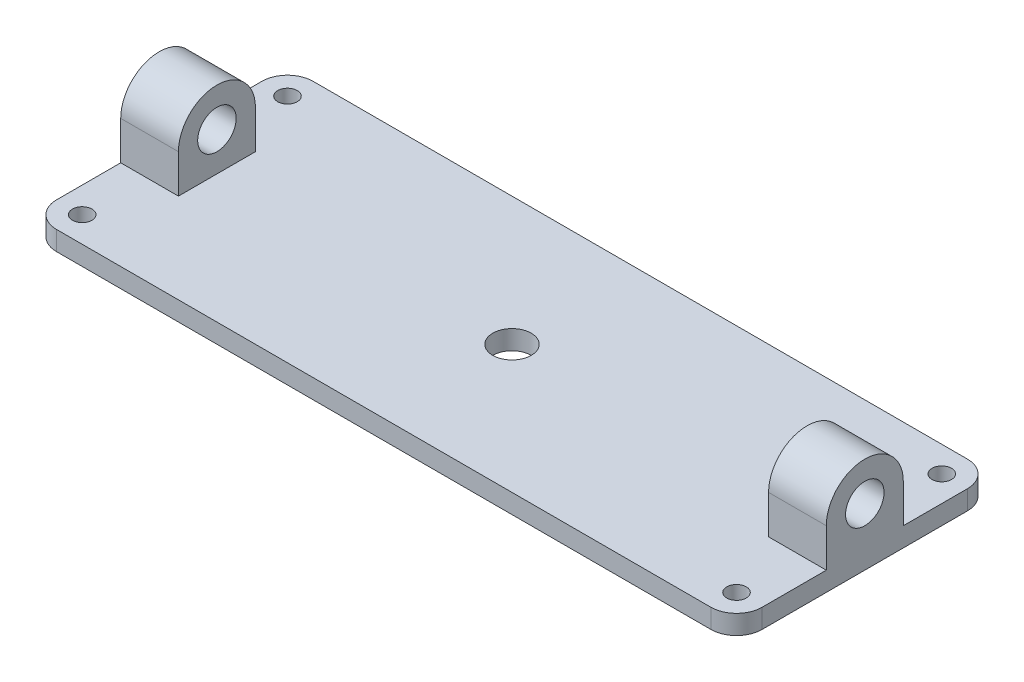
SolidWorks part; units mm, degrees
ref_plane "Front Plane" through (0, 0, 0) normal (0, 0, 1) x (1, 0, 0)
ref_plane "Top Plane" through (0, 0, 0) normal (0, 1, 0) x (1, 0, 0)
ref_plane "Right Plane" through (0, 0, 0) normal (1, 0, 0) x (0, 0, -1)
sketch "Sketch1" plane through (0, 0, 0) normal (0, 1, 0) x (1, 0, 0)
  line L0 (-349.25, 0) -> (349.25, 0) construction
  line L1 (-323.85, -127) -> (323.85, -127)
  line L2 (-349.25, -101.6) -> (-349.25, 101.6)
  line L3 (-323.85, 127) -> (323.85, 127)
  line L4 (349.25, -101.6) -> (349.25, 101.6)
  line L5 (-349.25, -127) -> (349.25, 127) construction
  line L6 (-349.25, 127) -> (349.25, -127) construction
  line L8 (-349.25, 38.1) -> (-292.1, 38.1)
  line L9 (-349.25, 38.1) -> (-349.25, -38.1)
  line L10 (-349.25, -38.1) -> (-292.1, -38.1)
  line L11 (-292.1, 38.1) -> (-292.1, -38.1)
  line L12 (349.25, 38.1) -> (292.1, 38.1)
  line L13 (349.25, 38.1) -> (349.25, -38.1)
  line L14 (349.25, -38.1) -> (292.1, -38.1)
  line L15 (292.1, 38.1) -> (292.1, -38.1)
  circle A0 centre (0, 0) radius 19.05
  arc A1 (-323.85, 127) -> (-349.25, 101.6) centre (-323.85, 101.6) ccw
  arc A2 (323.85, 127) -> (349.25, 101.6) centre (323.85, 101.6) cw
  arc A3 (323.85, -127) -> (349.25, -101.6) centre (323.85, -101.6) ccw
  arc A4 (-323.85, -127) -> (-349.25, -101.6) centre (-323.85, -101.6) cw
  circle A5 centre (-323.85, 101.6) radius 9.652
  circle A6 centre (-323.85, -101.6) radius 9.652
  circle A7 centre (323.85, -101.6) radius 9.652
  circle A8 centre (323.85, 101.6) radius 9.652
  point P0 (0, 0)
  point P34 (0, 0)
  point P35 (-292.1, 0)
  dimension "D3" = 25.4
  dimension "D4" = 25.4
  dimension "D5" = 19.304
  dimension "D6" = 38.1
  dimension "D1" = 698.5
  dimension "D2" = 254
  dimension "D7" = 76.2
  dimension "D8" = 57.15
extrude "Boss-Extrude1" add sketch "Sketch1" along normal blind 19.05 contours A4 L1 A3 L4 L14 L15 L12 A2 L3 A1 L2 L8 L11 L10 A8 A7 A6 A5 A0 region at (-336.555, 0, 114.305)
extrude "Boss-Extrude2" add sketch "Sketch1<3>" along normal blind 57.15 contours L11 L8 L2 L10 | L12 L15 L14 L4 region at (-320.675, 0, 0) region at (320.675, 0, 0)
sketch "Sketch1<3>" plane through (0, 0, 0) normal (0, 1, 0) x (1, 0, 0) same geometry as "Sketch1"
sketch "Sketch2" plane through (349.25, 0, 0) normal (1, 0, 0) x (0, 0, -1)
  line L0 (-38.1, 57.15) -> (38.1, 57.15) construction
  line L1 (38.1, 57.15) -> (-38.1, 57.15)
  circle A0 centre (0, 57.15) radius 19.05
  arc A1 (38.1, 57.15) -> (-38.1, 57.15) centre (0, 57.15) ccw
  line M7 (38.1, 57.15) -> (-38.1, 57.15)
  dimension "D1" = 38.1
extrude "Boss-Extrude3" add sketch "Sketch2" against normal blind 57.15 contours A1 A0 M7 region at (349.25, 58.0019, -28.575)
extrude "Cut-Extrude2" cut sketch "Sketch2<4>" against normal blind 57.15 contours L1 A0 region at (349.25, 49.0649, 0)
sketch "Sketch2<4>" plane through (349.25, 0, 0) normal (1, 0, 0) x (0, 0, -1) same geometry as "Sketch2"
mirror "Mirror1" about plane through (0, 0, 0) normal (1, 0, 0) of "Boss-Extrude3", "Cut-Extrude2"
